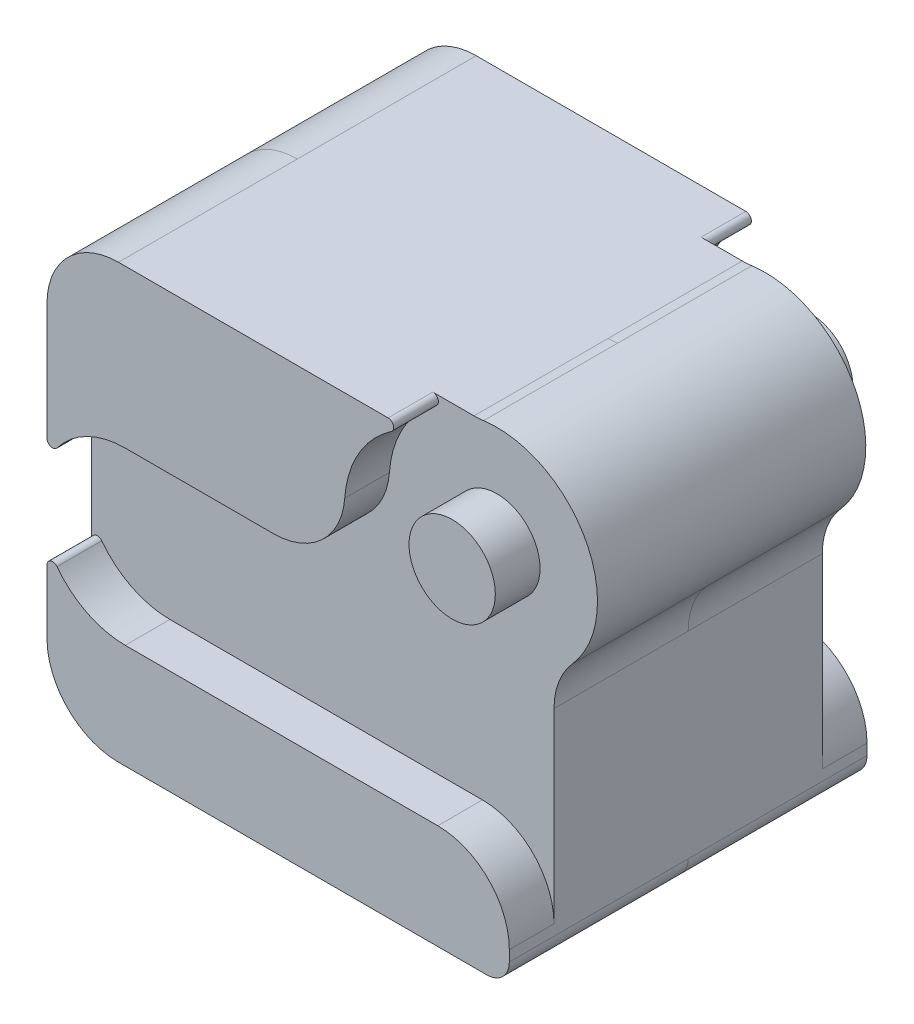
SolidWorks part; units mm, degrees
material "ABS"
ref_plane "Front Plane" through (0, 0, 0) normal (0, 0, 1) x (1, 0, 0)
ref_plane "Top Plane" through (0, 0, 0) normal (0, 1, 0) x (1, 0, 0)
ref_plane "Right Plane" through (0, 0, 0) normal (1, 0, 0) x (0, 0, -1)
sketch "Sketch1" plane through (0, 0, 0) normal (0, 0, 1) x (1, 0, 0)
  line L0 (0, 0) -> (9.1281, 0) construction
  line L1 (0, 0) -> (0, 9.1281) construction
  line L2 (0, 0) -> (12.5071, -2.2053) construction
  line L3 (0, 0) -> (-2.2053, 12.5071) construction
  line L4 (-1.5851, 8.9894) -> (-7.8386, 7.8868) construction
  line L5 (0, 5.5562) -> (-22.225, 5.5562) construction
  line L6 (0, 0) -> (-22.225, 0) construction
  line L7 (-22.225, 0) -> (-22.225, 5.5562) construction
  line L8 (-19.4469, 5.5562) -> (-10.5454, 5.5562)
  line L9 (-19.4469, 0) -> (-5.5562, 0)
  line L10 (-7.2184, 4.3692) -> (-8.4589, 11.4044) construction
  line L11 (-8.4589, 11.4044) -> (-2.2053, 12.5071)
  circle A0 centre (0, 0) radius 1.7859
  circle A1 centre (0, 0) radius 5.5562
  circle A2 centre (0, 0) radius 9.1281 construction
  circle A3 centre (-1.5851, 8.9894) radius 1.7859
  circle A4 centre (8.9894, -1.5851) radius 1.7859
  circle A5 centre (-7.8386, 7.8868) radius 1.7859
  circle A6 centre (8.9894, -1.5851) radius 3.5719
  circle A7 centre (-1.5851, 8.9894) radius 3.5719
  circle A8 centre (-7.8386, 7.8868) radius 3.5719
  circle A9 centre (-19.4469, 2.7781) radius 2.7781
  arc A10 (7.2306, -1.275) -> (-1.275, 7.2306) centre (0, 0) ccw
  arc A11 (10.7483, -1.8952) -> (-1.8952, 10.7483) centre (0, 0) ccw
  arc A12 (12.5071, -2.2053) -> (-2.2053, 12.5071) centre (0, 0) ccw
  point P24 (-22.225, 2.7781)
  point P35 (-7.8386, 7.8868)
  dimension "D4" = 7.1437
  dimension "D5" = 11.1125
  dimension "D6" = 3.5719
  dimension "D1" = 6.35
  dimension "D2" = 10
  dimension "D3" = 10
  dimension "D7" = 22.225
sketch "Sketch2" plane through (0, 0, 0) normal (0, 0, 1) x (1, 0, 0)
  line L0 (-7.2184, 4.3692) -> (-8.4589, 11.4044) construction
  line L1 (-8.4589, 11.4044) -> (-22.225, 11.4044)
  line L2 (-22.225, 11.4044) -> (-22.225, -5.5562)
  line L3 (-22.225, 0) -> (-22.225, 5.5562) construction
  line L5 (-22.225, -5.5562) -> (-5.8102, -5.5562)
  line L6 (-5.8102, -5.5562) -> (-5.8102, 4.9467)
  line L8 (-5.8102, -5.5562) -> (0, -5.5562) construction
  line L9 (-22.225, -3.9688) -> (-5.8102, -3.9688)
  circle A0 centre (-7.8386, 7.8868) radius 3.5719
  circle A1 centre (0, 0) radius 5.5562 construction
  circle A3 centre (-7.8386, 7.8868) radius 3.5719 construction
  dimension "D1" = 1.5875
  dimension "D3" = 0.254
extrude "Boss-Extrude1" add sketch "Sketch2" along normal blind 6.35 contours A0 L1 L2 L5 L6 | A0 region at (-14.9042, 3.0647, 0) region at (-7.8386, 7.8868, 0)
sketch "Sketch3" plane through (0, 0, 6.35) normal (0, 0, 1) x (1, 0, 0)
  line L0 (-19.4469, 5.8102) -> (-11.0519, 5.8102)
  line L1 (-19.4469, -0.254) -> (-5.8102, -0.254)
  line L2 (-5.8102, -3.9688) -> (-5.8102, 4.9467) construction
  line L3 (-5.8102, -0.254) -> (-5.8102, 4.6429)
  circle A0 centre (-19.4469, 2.7781) radius 3.0321
  circle A2 centre (-7.8386, 7.8868) radius 3.8259
  circle A3 centre (-7.8386, 7.8868) radius 3.5719 construction
  circle A4 centre (-19.4469, 2.7781) radius 2.7781 construction
  circle A5 centre (-7.8386, 7.8868) radius 1.5319
  circle A6 centre (-7.8386, 7.8868) radius 1.7859 construction
  line M4 (-5.8102, -3.9688) -> (-5.8102, 4.9467)
  arc M5 (-5.8102, 4.9467) -> (-8.4589, 11.4044) centre (-7.8386, 7.8868) ccw
  line M6 (-8.4589, 11.4044) -> (-22.225, 11.4044)
  line M7 (-22.225, 11.4044) -> (-22.225, -3.9688)
  dimension "D1" = 0.254
  dimension "D2" = 0.254
  dimension "D3" = 0.254
extrude "Cut-Extrude2" cut sketch "Sketch3" against normal blind 1.5875 contours A0 M7 | A2 L0 A0 L1 M4 | A2 M6 M4 M5 region at (-11.8485, 2.5118, 6.35) region at (-19.4049, 2.7781, 6.35) region at (-11.3975, 8.9739, 6.35)
fillet "Fillet1" radius 2.54 6 edges at (-22.225, 11.4044, 3.175) (-5.8102, 4.9467, 2.3812) (-8.4589, 11.4044, 2.3812) (-11.0519, 5.8102, 5.5562) (-5.8102, -0.254, 5.5562) (-22.225, -3.9688, 3.175)
fillet "Fillet2" radius 0.1984 3 edges at (-22.225, 1.5633, 5.5562) (-22.225, 3.993, 5.5562) (-9.3432, 11.4044, 5.5562)
fillet "Fillet3" radius 0.7937 1 edges at (-5.8102, -3.9688, 3.175)
mirror "Mirror1" about plane through (0, 0, 0) normal (0, 0, 1) of "Fillet3", "Fillet2", "Fillet1", "Boss-Extrude1", "Cut-Extrude2"
